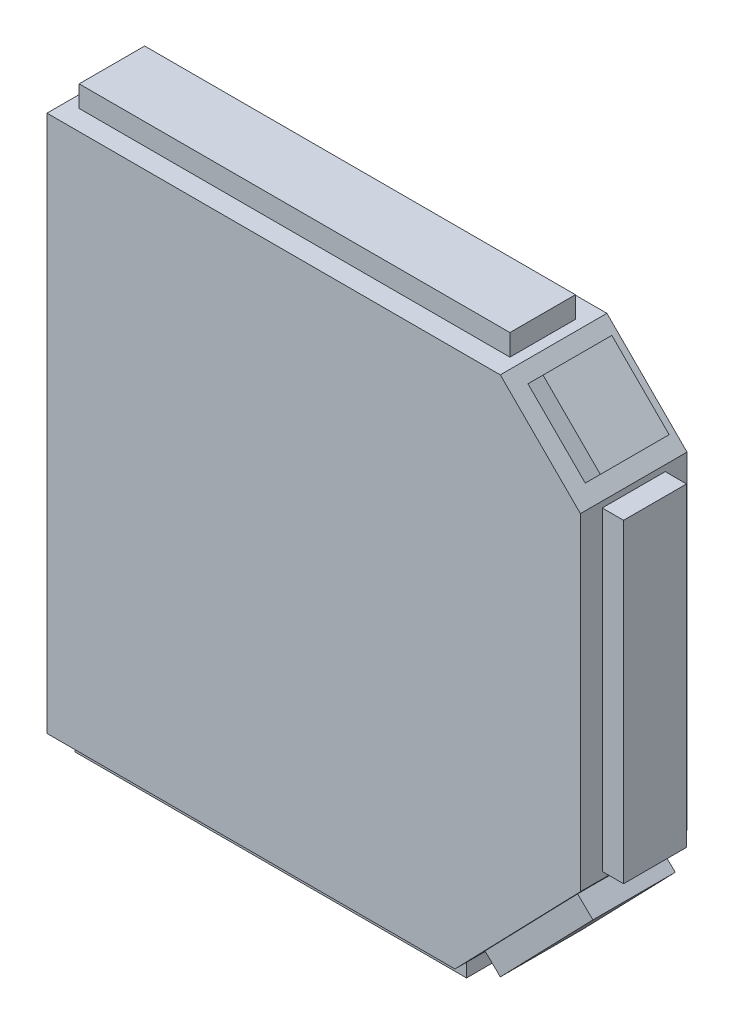
SolidWorks part; units mm, degrees
ref_plane "Front Plane" through (0, 0, 0) normal (0, 0, 1) x (1, 0, 0)
ref_plane "Top Plane" through (0, 0, 0) normal (0, 1, 0) x (1, 0, 0)
ref_plane "Right Plane" through (0, 0, 0) normal (1, 0, 0) x (0, 0, -1)
sketch "Sketch1" plane through (0, 0, 0) normal (0, 0, 1) x (1, 0, 0)
  line L0 (0, 0) -> (108, 0)
  line L1 (108, 0) -> (127.0919, -19.0919)
  line L2 (0, 0) -> (0, -128)
  line L3 (127.0919, -19.0919) -> (127.0919, -97.0919)
  line L4 (127.0919, -97.0919) -> (97.1931, -128)
  line L5 (0, -128) -> (97.1931, -128)
extrude "Boss-Extrude1" add sketch "Sketch1" along normal blind 25.4
sketch "Sketch2" plane through (0, 0, 0) normal (-1, 0, 0) x (0, 0, 1)
  line L1 (20.3296, -76.0035) -> (6.0877, -76.0035)
  line L2 (20.3296, -76.0035) -> (20.3296, -126.0035)
  line L3 (20.3296, -126.0035) -> (6.0877, -126.0035)
  line L4 (6.0877, -76.0035) -> (6.0877, -126.0035)
  line L5 (20.3296, -76.0035) -> (6.0877, -126.0035) construction
  line L6 (20.3296, -126.0035) -> (6.0877, -76.0035) construction
  point P0 (13.2086, -101.0035)
extrude "Cut-Extrude1" cut sketch "Sketch2" against normal blind 25.4
sketch "Sketch3" plane through (127.0919, 0, 0) normal (1, 0, 0) x (0, 0, -1)
  line L1 (-20.2, -20.5235) -> (-5.2, -20.5235)
  line L2 (-20.2, -20.5235) -> (-20.2, -95.5235)
  line L3 (-20.2, -95.5235) -> (-5.2, -95.5235)
  line L4 (-5.2, -20.5235) -> (-5.2, -95.5235)
  line L5 (-20.2, -20.5235) -> (-5.2, -95.5235) construction
  line L6 (-20.2, -95.5235) -> (-5.2, -20.5235) construction
  point P0 (-12.7, -58.0235)
extrude "Cut-Extrude2" cut sketch "Sketch3" against normal offset from surface (114.3919 mm away) 12.7 up to face at (0, -101.0035, 13.2086)
sketch "Sketch4" plane through (0, -128, 0) normal (0, -1, 0) x (-1, 0, 0)
  line L1 (-95.3514, -4.0169) -> (-2.0814, -4.0169)
  line L2 (-95.3514, -4.0169) -> (-95.3514, -20.7977)
  line L3 (-95.3514, -20.7977) -> (-2.0814, -20.7977)
  line L4 (-2.0814, -4.0169) -> (-2.0814, -20.7977)
  line L5 (-95.3514, -4.0169) -> (-2.0814, -20.7977) construction
  line L6 (-95.3514, -20.7977) -> (-2.0814, -4.0169) construction
  point P0 (-48.7164, -12.4073)
extrude "Cut-Extrude3" cut sketch "Sketch4" against normal blind 38.1
sketch "Sketch5" plane through (0, 0, 0) normal (0, 1, 0) x (1, 0, 0)
  line L1 (105.4979, -20.6026) -> (2.8619, -20.6026)
  line L2 (105.4979, -20.6026) -> (105.4979, -4.9925)
  line L3 (105.4979, -4.9925) -> (2.8619, -4.9925)
  line L4 (2.8619, -20.6026) -> (2.8619, -4.9925)
  line L5 (105.4979, -20.6026) -> (2.8619, -4.9925) construction
  line L6 (105.4979, -4.9925) -> (2.8619, -20.6026) construction
  point P0 (54.1799, -12.7976)
extrude "Cut-Extrude4" cut sketch "Sketch5" against normal blind 101.6
sketch "Sketch6" plane through (54, 54, 0) normal (0.7071, 0.7071, 0) x (0, 0, -1)
  line L1 (-4.9925, -99.3201) -> (-21.3831, -99.3201)
  line L2 (-4.9925, -99.3201) -> (-4.9925, -80.0037)
  line L3 (-4.9925, -80.0037) -> (-21.3831, -80.0037)
  line L4 (-21.3831, -99.3201) -> (-21.3831, -80.0037)
  line L5 (-4.9925, -99.3201) -> (-21.3831, -80.0037) construction
  line L6 (-4.9925, -80.0037) -> (-21.3831, -99.3201) construction
  point P0 (-13.1878, -89.6619)
extrude "Cut-Extrude5" cut sketch "Sketch6" against normal blind 25.4
sketch "Sketch7" plane through (114.1741, -110.4457, 0) normal (0.7187, -0.6953, 0) x (0, 0, -1)
  line L1 (-2.8245, -18.3747) -> (-22.447, -18.3747)
  line L2 (-2.8245, -18.3747) -> (-2.8245, 13.3599)
  line L3 (-2.8245, 13.3599) -> (-22.447, 13.3599)
  line L4 (-22.447, -18.3747) -> (-22.447, 13.3599)
  line L5 (-2.8245, -18.3747) -> (-22.447, 13.3599) construction
  line L6 (-2.8245, 13.3599) -> (-22.447, -18.3747) construction
  point P0 (-12.6357, -2.5074)
extrude "Cut-Extrude6" cut sketch "Sketch7" against normal blind 25.4
ref_plane "Plane1" through (0, -126.0035, 6.0877) normal (0, -1, 0) x (-1, 0, 0)
extrude "Boss-Extrude2" add sketch "Sketch4<2>" along normal blind 5.08 separate body
sketch "Sketch4<2>" plane through (0, -128, 0) normal (0, -1, 0) x (-1, 0, 0) same geometry as "Sketch4"
extrude "Boss-Extrude4" add sketch "Sketch5<2>" along normal blind 5.08 separate body
sketch "Sketch5<2>" plane through (0, 0, 0) normal (0, 1, 0) x (1, 0, 0) same geometry as "Sketch5"
extrude "Boss-Extrude5" add sketch "Sketch7<2>" along normal blind 5.08 separate body
sketch "Sketch7<2>" plane through (114.1741, -110.4457, 0) normal (0.7187, -0.6953, 0) x (0, 0, -1) same geometry as "Sketch7"
extrude "Boss-Extrude6" add sketch "Sketch6<2>" along normal blind 5.08 separate body
sketch "Sketch6<2>" plane through (54, 54, 0) normal (0.7071, 0.7071, 0) x (0, 0, -1) same geometry as "Sketch6"
extrude "Boss-Extrude7" add sketch "Sketch3<2>" along normal blind 5.08 separate body
sketch "Sketch3<2>" plane through (127.0919, 0, 0) normal (1, 0, 0) x (0, 0, -1) same geometry as "Sketch3"
extrude "Boss-Extrude8" add sketch "Sketch2<3>" along normal blind 5.08 separate body
sketch "Sketch2<3>" plane through (0, 0, 0) normal (-1, 0, 0) x (0, 0, 1) same geometry as "Sketch2"
